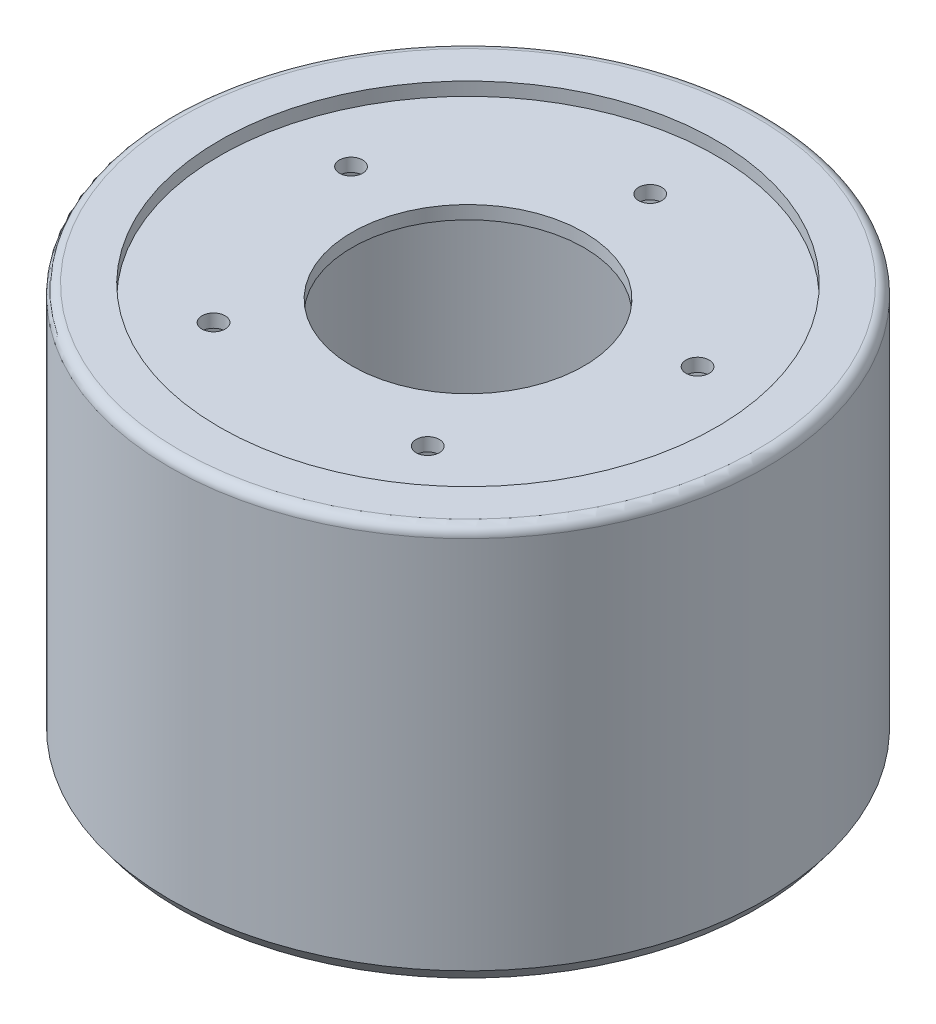
SolidWorks part; units mm, degrees
ref_plane "Front Plane" through (0, 0, 0) normal (0, 0, 1) x (1, 0, 0)
ref_plane "Top Plane" through (0, 0, 0) normal (0, 1, 0) x (1, 0, 0)
ref_plane "Right Plane" through (0, 0, 0) normal (1, 0, 0) x (0, 0, -1)
sketch "Sketch3" plane through (0, 0, 0) normal (0, 1, 0) x (1, 0, 0)
  circle A0 centre (0, 0) radius 45
  circle A1 centre (0, 0) radius 37.5
  circle A2 centre (0, 0) radius 17.5
  circle A3 centre (0, 0) radius 27.5
  circle A9 centre (0, 27.5) radius 1.75
  circle A10 centre (26.1541, 8.498) radius 1.75
  circle A11 centre (16.1641, -22.248) radius 1.75
  circle A12 centre (-16.1641, -22.248) radius 1.75
  circle A13 centre (-26.1541, 8.498) radius 1.75
  point P18 (1.7205, -1.25)
  point P19 (0, 0)
  dimension "D1" = 35
  dimension "D2" = 75
  dimension "D3" = 90
  dimension "D4" = 55
  dimension "D6" = 3.5
  dimension "D5" = 5
extrude "Boss-Extrude1" add sketch "Sketch3" along normal blind 60 contours A0 A1 region at (-43.7272, 0, 0)
fillet "Fillet1" radius 1.5 1 edges at (0, 60, 45)
extrude "Boss-Extrude3" add sketch "Sketch3<6>" along normal blind 2 from offset 56 contours A13 A3 A12 A11 A10 A9 A2 | A1 A13 A3 A9 A10 A11 A12 region at (-36.4393, 0, 0) region at (24.1839, 0, 11.3681)
sketch "Sketch3<6>" plane through (0, 0, 0) normal (0, 1, 0) x (1, 0, 0) same geometry as "Sketch3"
sketch "Sketch5" plane through (0, 0, 0) normal (0, 1, 0) x (1, 0, 0)
  circle A0 centre (0, 0) radius 39
  dimension "D1" = 78
extrude "Cut-Extrude1" cut sketch "Sketch5" along normal blind 12
chamfer "Chamfer1" distance 1.5 1 edges at (0, 12, 37.5)
chamfer "Chamfer2" distance 1.5 distance2 2 1 edges at (0, 0, 45) first distance on face at (0, 0, 39)
